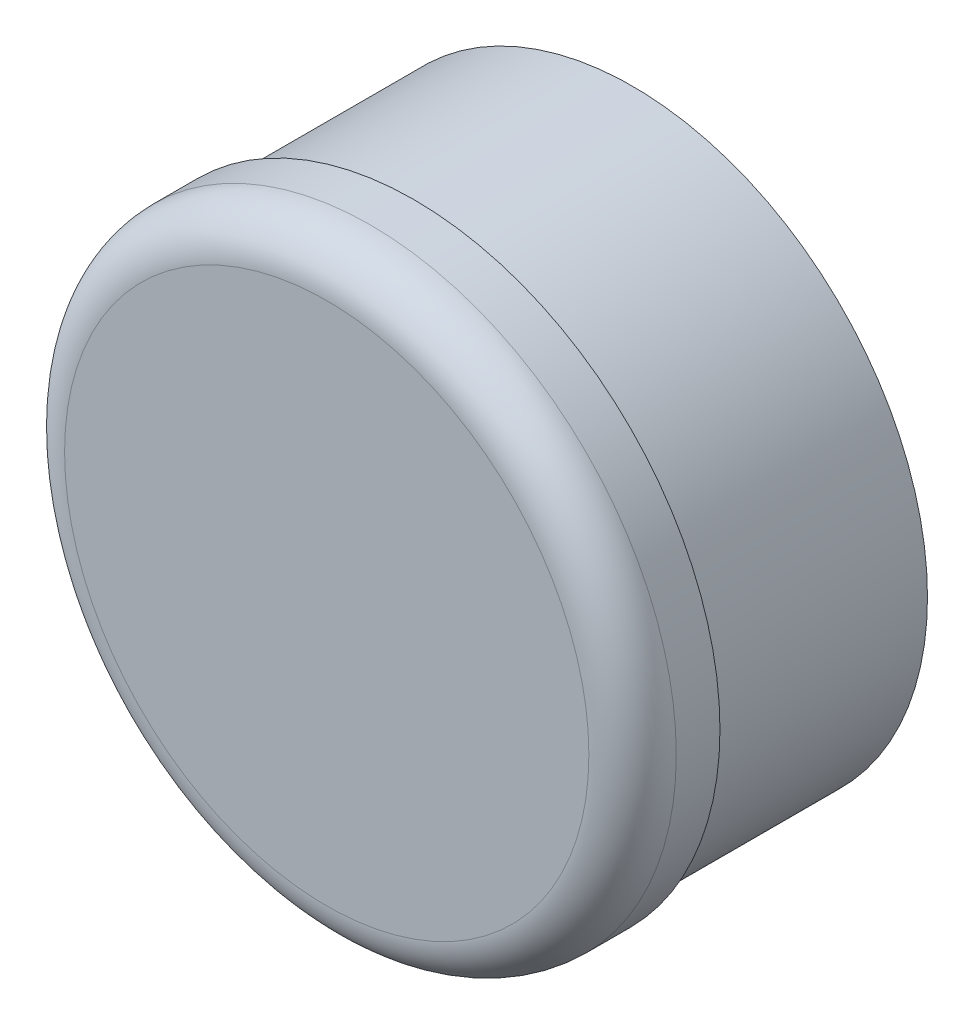
SolidWorks part; units mm, degrees
ref_plane "前视基准面" through (0, 0, 0) normal (0, 0, 1) x (1, 0, 0)
ref_plane "上视基准面" through (0, 0, 0) normal (0, 1, 0) x (1, 0, 0)
ref_plane "右视基准面" through (0, 0, 0) normal (1, 0, 0) x (0, 0, -1)
sketch "草图1" plane through (0, 0, 0) normal (0, 0, 1) x (1, 0, 0)
  circle A0 centre (0, 0) radius 1.75
  circle A1 centre (0, 0) radius 6.75
  dimension "D1" = 3.5
  dimension "D2" = 13.5
extrude "凸台-拉伸1" add sketch "草图1" along normal blind 5
sketch "草图2" plane through (0, 0, 5) normal (0, 0, 1) x (1, 0, 0)
  circle A0 centre (0, 0) radius 7
  dimension "D1" = 14
extrude "凸台-拉伸2" add sketch "草图2" along normal blind 2
fillet "圆角1" radius 1 1 edges at (7, 0, 7)
